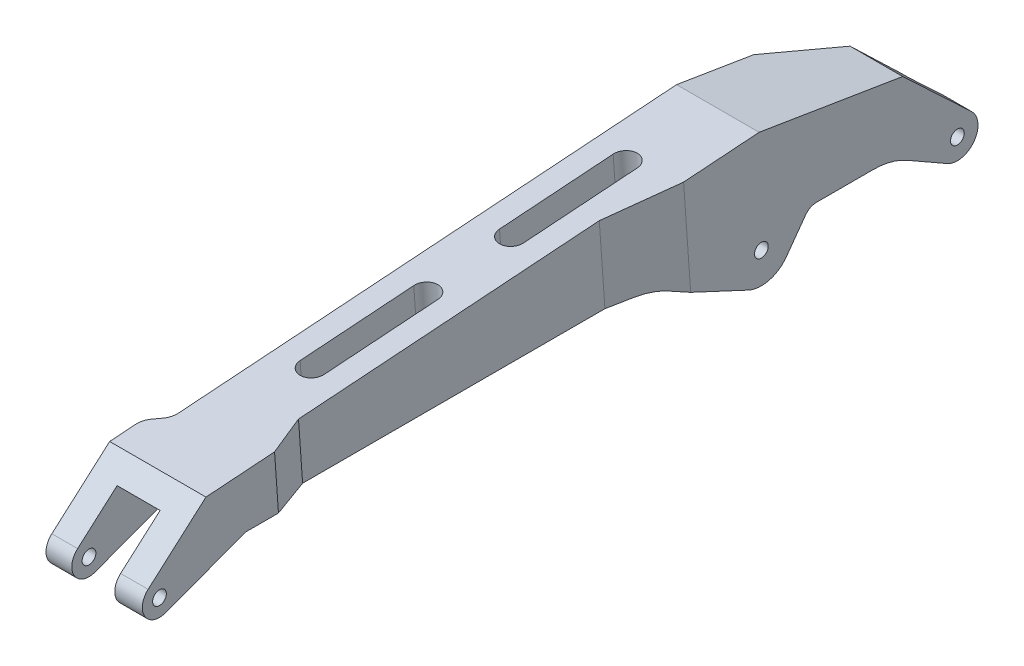
SolidWorks part; units mm, degrees
ref_plane "Plan de face" through (0, 0, 0) normal (0, 0, 1) x (1, 0, 0)
ref_plane "Plan de dessus" through (0, 0, 0) normal (0, 1, 0) x (1, 0, 0)
ref_plane "Plan de droite" through (0, 0, 0) normal (1, 0, 0) x (0, 0, -1)
sketch "Sketch1" plane through (0, 0, 0) normal (1, 0, 0) x (0, 0, -1)
  line L0 (-149.9079, 4) -> (-173.2566, -4.6862)
  line L8 (-34.3077, 4) -> (-149.9079, 4)
  line L12 (-3.8036, -8.1568) -> (-25.8554, 2.1262)
  line L13 (12.8503, 2.4104) -> (7.2926, -5.2742)
  line L15 (32.5383, 4.0311) -> (16.0227, 4.0311)
  line L16 (54.0258, -5.2082) -> (42.4563, 1.3987)
  line L17 (41.089, 23.1881) -> (61.1079, 4.37)
  line L22 (-0.6535, 30.0125) -> (41.089, 23.1881)
  line L24 (-161.4914, 18.5783) -> (-0.6535, 30.0125)
  line L29 (-178.307, 3.7502) -> (-161.4914, 18.5783)
  arc A10 (-25.8554, 2.1262) -> (-34.3077, 4) centre (-34.3077, -16) ccw
  arc A11 (-3.8036, -8.1568) -> (7.2926, -5.2742) centre (0, 0) ccw
  arc A12 (42.4563, 1.3987) -> (32.5383, 4.0311) centre (32.5383, -15.9689) ccw
  arc A13 (54.0258, -5.2082) -> (61.1079, 4.37) centre (57, 0) ccw
  arc A17 (-178.307, 3.7502) -> (-173.2566, -4.6862) centre (-175, 0) ccw
  arc A18 (12.8503, 2.4104) -> (16.0227, 4.0311) centre (16.0227, 0.1161) cw
  circle A19 centre (0, 0) radius 2
  circle A20 centre (57, 0) radius 2
  circle A21 centre (-175, 0) radius 2
  dimension "D1" = 4
  dimension "D2" = 5
  dimension "D3" = 9
  dimension "D4" = 5.9976
  dimension "D5" = 57
  dimension "D6" = 175
  dimension "D7" = 24.9122
  dimension "D8" = 22.4195
  dimension "D9" = 24.3315
  dimension "D10" = 9.4837
  dimension "D11" = 27.475
  dimension "D12" = 42.2967
  dimension "D13" = 21
  dimension "D14" = 13.5
extrude "Boss-Extrude1" add sketch "Sketch1" along normal mid plane 24
sketch "Sketch2" plane through (0, 29.1272, -4.7619) normal (0, 0.9869, -0.1613) x (1, 0, 0)
  line L0 (12, 62.2508) -> (-12, 62.2508) construction
  line L1 (-12, 62.2508) -> (-12, 54.1582) construction
  line L2 (-12, 59.6022) -> (-12, 36.8094) construction
  line L3 (3.5, 62.2508) -> (-12, 62.2508) construction
  line L4 (-12, 62.2508) -> (-12, 54.1582) construction
  line L5 (-12, 59.6022) -> (-12, 36.8094) construction
  line L6 (-12, 36.8094) -> (-12, -5.4873) construction
  line L7 (-12, 36.8094) -> (-12, 17.2508) construction
  line L8 (3.5, 62.2508) -> (3.5, 52.0644)
  line L9 (3.5, 52.0644) -> (-12, 17.2508)
  line L10 (12, 59.6022) -> (12, 36.8094) construction
  line L11 (-12, 17.2508) -> (-12, 62.2508)
  line L12 (-12, 62.2508) -> (3.5, 62.2508)
  dimension "D1" = 8.5
  dimension "D2" = 156
  dimension "D3" = 45
extrude "Cut-Extrude1" cut sketch "Sketch2" against normal through all
sketch "Sketch5" plane through (-12, 0, 0) normal (-1, 0, 0) x (0, 0, 1)
  line L0 (173.2566, -4.6862) -> (149.9079, 4) construction
  line L1 (161.4914, 18.5783) -> (178.307, 3.7502) construction
  line L2 (173.2566, -4.6862) -> (149.9079, 4)
  line L3 (161.4914, 18.5783) -> (178.307, 3.7502)
  line L4 (161.4914, 18.5783) -> (148.4914, 19.5025)
  line L5 (0.6535, 30.0125) -> (161.4914, 18.5783) construction
  line L6 (148.4914, 19.5025) -> (136.9079, 4)
  line L7 (149.9079, 4) -> (34.3077, 4) construction
  line L8 (136.9079, 4) -> (149.9079, 4)
  arc A0 (173.2566, -4.6862) -> (178.307, 3.7502) centre (175, 0) ccw construction
  circle A1 centre (175, 0) radius 2 construction
  arc A2 (173.2566, -4.6862) -> (178.307, 3.7502) centre (175, 0) ccw
  circle A3 centre (175, 0) radius 2
  dimension "D1" = 13
  dimension "D2" = 13
extrude "Boss-Extrude3" add sketch "Sketch5" along normal blind 4
ref_plane "Plane1" through (4, 0, 0) normal (1, 0, 0) x (0, 0, -1)
sketch "Sketch6" plane through (4, 0, 0) normal (1, 0, 0) x (0, 0, -1)
  line L0 (-178.307, 3.7502) -> (-166.8214, 13.8783)
  line L2 (-149.9079, 4) -> (-173.2566, -4.6862)
  line L3 (-173.2566, -4.6862) -> (-149.9079, 4) construction
  line L4 (-161.4914, 18.5783) -> (-178.307, 3.7502) construction
  line L5 (-166.8214, 13.8783) -> (50.9929, 13.8783)
  line L6 (-149.9079, 4) -> (-34.3077, 4) construction
  line L7 (-149.9079, 4) -> (-34.3077, 4)
  line L8 (16.0227, 4.0311) -> (32.5383, 4.0311) construction
  line L9 (7.2926, -5.2742) -> (12.8503, 2.4104) construction
  line L10 (-25.8554, 2.1262) -> (-3.8036, -8.1568) construction
  line L11 (16.0227, 4.0311) -> (32.5383, 4.0311)
  line L12 (7.2926, -5.2742) -> (12.8503, 2.4104)
  line L13 (-25.8554, 2.1262) -> (-3.8036, -8.1568)
  line L14 (61.1079, 4.37) -> (41.089, 23.1881) construction
  line L15 (42.4563, 1.3987) -> (54.0258, -5.2082) construction
  line L16 (61.1079, 4.37) -> (50.9929, 13.8783)
  line L17 (42.4563, 1.3987) -> (54.0258, -5.2082)
  arc A0 (-178.307, 3.7502) -> (-173.2566, -4.6862) centre (-175, 0) ccw construction
  arc A1 (-178.307, 3.7502) -> (-173.2566, -4.6862) centre (-175, 0) ccw
  arc A2 (16.0227, 4.0311) -> (12.8503, 2.4104) centre (16.0227, 0.1161) ccw construction
  arc A3 (-3.8036, -8.1568) -> (7.2926, -5.2742) centre (0, 0) ccw construction
  arc A4 (-25.8554, 2.1262) -> (-34.3077, 4) centre (-34.3077, -16) ccw construction
  arc A5 (16.0227, 4.0311) -> (12.8503, 2.4104) centre (16.0227, 0.1161) ccw
  arc A6 (-3.8036, -8.1568) -> (7.2926, -5.2742) centre (0, 0) ccw
  arc A7 (-25.8554, 2.1262) -> (-34.3077, 4) centre (-34.3077, -16) ccw
  arc A8 (54.0258, -5.2082) -> (61.1079, 4.37) centre (57, 0) ccw construction
  arc A9 (42.4563, 1.3987) -> (32.5383, 4.0311) centre (32.5383, -15.9689) ccw construction
  arc A10 (54.0258, -5.2082) -> (61.1079, 4.37) centre (57, 0) ccw
  arc A11 (42.4563, 1.3987) -> (32.5383, 4.0311) centre (32.5383, -15.9689) ccw
  dimension "D1" = 4.7
extrude "Cut-Extrude2" cut sketch "Sketch6" against normal blind 12.5
chamfer "Chamfer1" distance 3 angle 45 1 edges at (-16, 11.7513, 142.6997)
fillet "Fillet1" radius 4 2 edges at (-12, 11.7513, 142.6997) (-16, 11.6249, 146.3502)
sketch "Sketch7" plane through (0, 29.9078, 2.1262) normal (0, 0.9975, 0.0709) x (1, 0, 0)
  line L2 (0, -97.5373) -> (76.083, -97.5373) construction
  line L10 (12, -139.7675) -> (8, -128.7776)
  line L11 (12, 1.4764) -> (12, -159.7675) construction
  line L12 (8, -128.7776) -> (8, -41.1018)
  line L13 (8, -41.1018) -> (12, -20.5236)
  line L14 (12, -20.5236) -> (12, -139.7675)
  line L15 (12, -159.7675) -> (-16, -159.7675) construction
  dimension "D4" = 4
  dimension "D5" = 20
  dimension "D6" = 22
  dimension "D7" = 169
  dimension "D8" = 160
extrude "Cut-Extrude3" cut sketch "Sketch7" against normal through all
sketch "Sketch8" plane through (0, 29.9078, 2.1262) normal (0, 0.9975, 0.0709) x (1, 0, 0)
  line L0 (-2, -139.7675) -> (-2, 1.4764) construction
  line L1 (-12, 1.4764) -> (-12, -143.5906) construction
  line L2 (8, -41.1018) -> (8, -128.7776) construction
  line L3 (8, -41.1018) -> (8, -128.7776) construction
  line L4 (-12, 1.4764) -> (-12, -143.5906) construction
  line L5 (12, 1.4764) -> (-12, 1.4764) construction
  line L6 (12, 1.4764) -> (-12, 1.4764) construction
  line L7 (12, -139.7675) -> (-12, -139.7675) construction
  line L8 (-2, -114.7675) -> (-2, -81.6455) construction
  line L9 (-2, -56.6455) -> (-2, -23.5236) construction
  line L10 (-5.5, -56.6455) -> (-5.5, -23.5236)
  line L11 (1.5, -56.6455) -> (1.5, -23.5236)
  line L12 (-5.5, -114.7675) -> (-5.5, -81.6455)
  line L13 (1.5, -114.7675) -> (1.5, -81.6455)
  arc A0 (-5.5, -56.6455) -> (1.5, -56.6455) centre (-2, -56.6455) ccw
  arc A1 (1.5, -23.5236) -> (-5.5, -23.5236) centre (-2, -23.5236) ccw
  arc A2 (-5.5, -114.7675) -> (1.5, -114.7675) centre (-2, -114.7675) ccw
  arc A3 (1.5, -81.6455) -> (-5.5, -81.6455) centre (-2, -81.6455) ccw
  point P8 (-2, -40.0846)
  point P20 (-2, -98.2065)
  dimension "D1" = 10
  dimension "D2" = 20
  dimension "D3" = 25
  dimension "D6" = 7
  dimension "D9" = 25
  dimension "D4" = 25
extrude "Cut-Extrude4" cut sketch "Sketch8" against normal through all
equation "\"Longueur1\"= 150mm"
equation "\"Longueur2\"= 175mm"
equation "\"D6@Sketch1\"=\"Longueur2\""
equation "\"D2@Sketch5\"=\"D1@Sketch5\""
equation "\"D1@Sketch8\"=\"D2@Sketch8\"/2"
